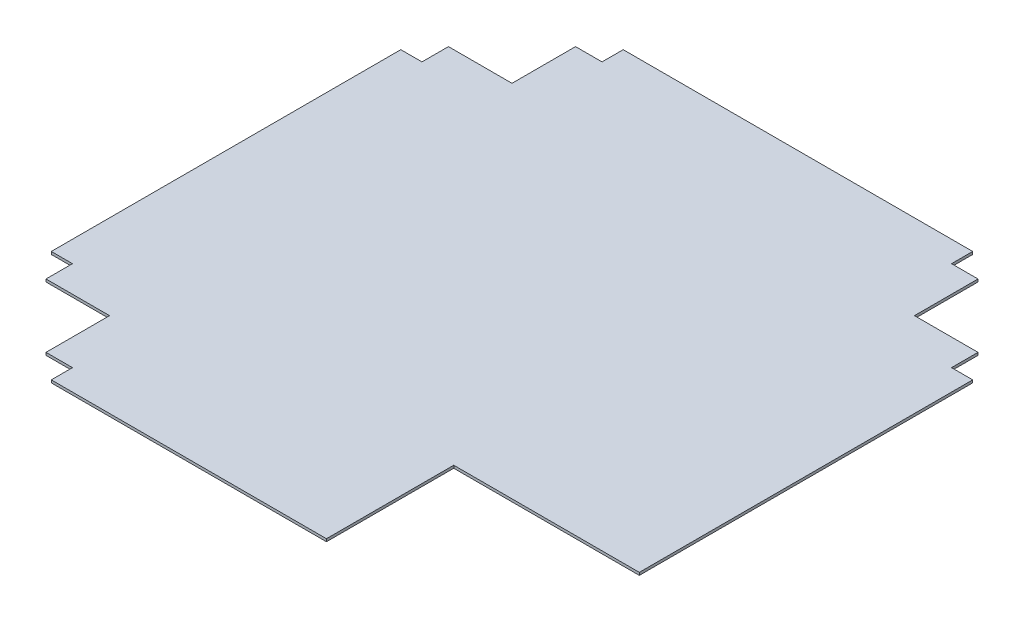
SolidWorks part; units mm, degrees
material "ABS PC"
ref_plane "Front Plane" through (0, 0, 0) normal (0, 0, 1) x (1, 0, 0)
ref_plane "Top Plane" through (0, 0, 0) normal (0, 1, 0) x (1, 0, 0)
ref_plane "Right Plane" through (0, 0, 0) normal (1, 0, 0) x (0, 0, -1)
sketch "Sketch1" plane through (0, 0, 0) normal (0, 1, 0) x (1, 0, 0)
  line L1 (-342.9, -342.9) -> (342.9, -342.9)
  line L2 (-342.9, -342.9) -> (-342.9, 342.9)
  line L3 (-342.9, 342.9) -> (342.9, 342.9)
  line L4 (342.9, -342.9) -> (342.9, 342.9)
  line L5 (-342.9, -342.9) -> (342.9, 342.9) construction
  line L6 (-342.9, 342.9) -> (342.9, -342.9) construction
  point P0 (0, 0)
  dimension "D1" = 685.8
extrude "Boss-Extrude1" add sketch "Sketch1" along normal blind 3.175
sketch "Sketch3" plane through (0, 3.175, 0) normal (0, 1, 0) x (1, 0, 0)
  line L1 (-342.9, 342.9) -> (-209.55, 342.9)
  line L2 (-342.9, 342.9) -> (-342.9, 209.55)
  line L3 (-342.9, 209.55) -> (-317.5, 209.55)
  line L4 (-209.55, 342.9) -> (-209.55, 317.5)
  line L18 (-209.55, 317.5) -> (-241.3, 317.5)
  line L19 (-241.3, 317.5) -> (-241.3, 241.3)
  line L20 (-241.3, 241.3) -> (-317.5, 241.3)
  line L21 (-317.5, 241.3) -> (-317.5, 209.55)
  line L23 (0, -55) -> (0, 55) construction
  line L24 (317.5, 241.3) -> (317.5, 209.55)
  line L25 (241.3, 241.3) -> (317.5, 241.3)
  line L26 (241.3, 317.5) -> (241.3, 241.3)
  line L27 (209.55, 317.5) -> (241.3, 317.5)
  line L28 (209.55, 342.9) -> (209.55, 317.5)
  line L29 (342.9, 209.55) -> (317.5, 209.55)
  line L30 (342.9, 342.9) -> (342.9, 209.55)
  line L31 (342.9, 342.9) -> (209.55, 342.9)
  line L32 (-55, 0) -> (55, 0) construction
  line L33 (342.9, -342.9) -> (209.55, -342.9)
  line L34 (342.9, -342.9) -> (342.9, -209.55)
  line L35 (342.9, -209.55) -> (317.5, -209.55)
  line L36 (209.55, -342.9) -> (209.55, -317.5)
  line L37 (209.55, -317.5) -> (241.3, -317.5)
  line L38 (241.3, -317.5) -> (241.3, -241.3)
  line L39 (241.3, -241.3) -> (317.5, -241.3)
  line L40 (317.5, -241.3) -> (317.5, -209.55)
  line L41 (-317.5, -241.3) -> (-317.5, -209.55)
  line L42 (-241.3, -241.3) -> (-317.5, -241.3)
  line L43 (-241.3, -317.5) -> (-241.3, -241.3)
  line L44 (-209.55, -317.5) -> (-241.3, -317.5)
  line L45 (-209.55, -342.9) -> (-209.55, -317.5)
  line L46 (-342.9, -209.55) -> (-317.5, -209.55)
  line L47 (-342.9, -342.9) -> (-342.9, -209.55)
  line L48 (-342.9, -342.9) -> (-209.55, -342.9)
  dimension "D1" = 133.35
  dimension "D2" = 76.2
  dimension "D3" = 25.4
extrude "Cut-Extrude1" cut sketch "Sketch3" against normal through all
extrude "Cut-Extrude2" cut sketch "Sketch4" against normal through all
sketch "Sketch4" plane through (0, 3.175, 0) normal (0, 1, 0) x (1, 0, 0)
  line L0 (387.096, -355.346) -> (120.396, -355.346)
  line L1 (120.396, -355.346) -> (120.396, -190.246)
  line L6 (120.396, -190.246) -> (387.096, -190.246)
  line L7 (387.096, -190.246) -> (387.096, -355.346)
